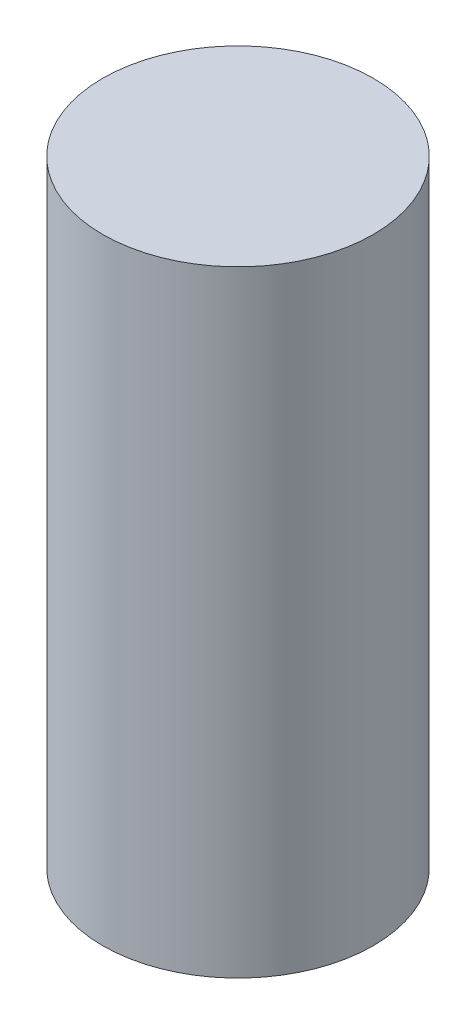
SolidWorks part; units mm, degrees
ref_plane "Front Plane" through (0, 0, 0) normal (0, 0, 1) x (1, 0, 0)
ref_plane "Top Plane" through (0, 0, 0) normal (0, 1, 0) x (1, 0, 0)
ref_plane "Right Plane" through (0, 0, 0) normal (1, 0, 0) x (0, 0, -1)
sketch "Sketch1" plane through (0, 0, 0) normal (0, 1, 0) x (1, 0, 0)
  line L0 (284.2974, 199.1145) -> (335.6873, 199.1145) construction
  line L1 (-27.4588, 43.4177) -> (32.5412, 43.4177)
  line L2 (32.5412, 43.4177) -> (32.5412, -16.3494)
  line L3 (32.5412, -16.3494) -> (-27.4588, -16.3494)
  line L4 (-27.4588, -16.3494) -> (-27.4588, 43.4177)
  circle A0 centre (2.6009, 13.789) radius 22.4041
  point P8 (2.6009, 13.789)
  point P9 (0, 0)
  dimension "D2" = 44.8082
  dimension "D1" = 60
extrude "Boss-Extrude1" add sketch "Sketch1" along normal blind 102 contours A0 region at (2.6009, 0, -13.789)
